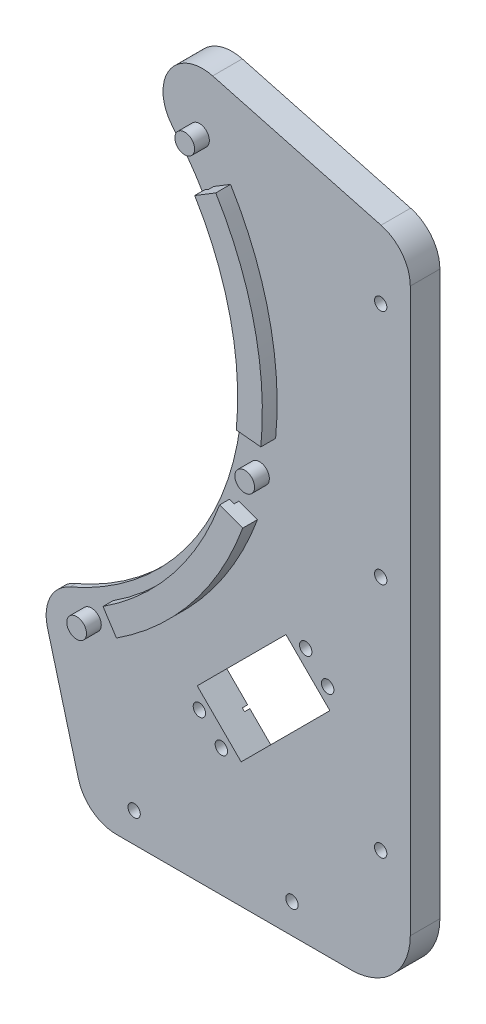
SolidWorks part; units mm, degrees
ref_plane "Front Plane" through (0, 0, 0) normal (0, 0, 1) x (1, 0, 0)
ref_plane "Top Plane" through (0, 0, 0) normal (0, 1, 0) x (1, 0, 0)
ref_plane "Right Plane" through (0, 0, 0) normal (1, 0, 0) x (0, 0, -1)
other "Configuration Table"
sketch "Sketch1" plane through (0, 0, 0) normal (0, 0, 1) x (1, 0, 0)
  line L3 (0, 0) -> (0, 95.25) construction
  line L4 (0, -106.7771) -> (0, 106.7771) construction
  line L5 (0, 0) -> (74.4694, 59.3874) construction
  line L6 (0, 0) -> (92.8619, -21.1951) construction
  line L7 (0, 0) -> (41.3274, -85.8173) construction
  line L8 (0, 0) -> (-41.3274, -85.8173) construction
  line L9 (0, 0) -> (-92.8619, -21.1951) construction
  line L10 (0, 0) -> (-74.4694, 59.3874) construction
  line L11 (-88.1918, 53.5711) -> (-82.7647, 50.2744)
  line L13 (-96.3816, -9.3854) -> (-102.7017, -10.0009)
  line L14 (-90.909, -33.3624) -> (-96.8703, -35.5502)
  line L15 (-56.2145, -86.5309) -> (-52.7551, -81.2059)
  circle A0 centre (0, 0) radius 95.25 construction
  circle A1 centre (-78.1929, 62.3568) radius 3.175
  circle A2 centre (-78.1929, 62.3568) radius 4.7625 construction
  circle A3 centre (-97.505, -22.2549) radius 3.175
  circle A4 centre (-97.505, -22.2549) radius 4.7625 construction
  circle A5 centre (-43.3938, -90.1081) radius 3.175
  circle A6 centre (-43.3938, -90.1081) radius 4.7625 construction
  circle A7 centre (0, 0) radius 96.8375 construction
  arc A8 (-82.7647, 50.2744) -> (-96.3816, -9.3854) centre (0, 0) ccw
  arc A9 (-88.1918, 53.5711) -> (-102.7017, -10.0009) centre (0, 0) ccw
  arc A10 (-56.2145, -86.5309) -> (-96.8703, -35.5502) centre (0, 0) cw
  arc A11 (-52.7551, -81.2059) -> (-90.909, -33.3624) centre (0, 0) cw
  point P23 (0, 0)
  dimension "D1" = 190.5
  dimension "D2" = 9.525
  dimension "D3" = 6.35
  dimension "D4" = 7
  dimension "D5" = 6.35
  dimension "D6" = 12.7
  dimension "D7" = 12.7
extrude "Boss-Extrude1" add sketch "Sketch1" along normal blind 4.7625
sketch "Sketch2" plane through (0, 0, 0) normal (0, 0, 1) x (1, 0, 0)
  line L0 (0, 0) -> (-41.3274, -85.8173) construction
  line L1 (0, 0) -> (-92.8619, -21.1951) construction
  line L2 (0, 0) -> (-74.4694, 59.3874) construction
  line L3 (0, 0) -> (-41.3274, -85.8173) construction
  line L4 (0, 0) -> (-92.8619, -21.1951) construction
  line L5 (0, 0) -> (-74.4694, 59.3874) construction
  line L6 (-82.4301, 80.9271) -> (-136.637, 66.4024)
  line L7 (127, 127) -> (-127, 127) construction
  line L8 (127, 127) -> (127, -127) construction
  line L9 (127, -127) -> (-127, -127) construction
  line L10 (-127, 127) -> (-127, -127) construction
  line L11 (127, 127) -> (-127, -127) construction
  line L12 (127, -127) -> (-127, 127) construction
  line L13 (-146.05, 54.1351) -> (-146.05, -127)
  line L14 (-127, -146.05) -> (-51.4696, -146.05)
  line L15 (-39.2023, -136.637) -> (-29.2478, -99.4863)
  line L16 (-127, 44.45) -> (-146.05, 44.45) construction
  line L17 (-107.95, -127) -> (-107.95, -146.05) construction
  line L18 (-136.525, 44.45) -> (-136.525, -107.95) construction
  circle A0 centre (0, 0) radius 95.25 construction
  circle A1 centre (0, 0) radius 95.25 construction
  arc A2 (-69.55, 60.3374) -> (-36.4829, -84.5388) centre (0, 0) ccw
  arc A3 (-36.4829, -84.5388) -> (-29.2478, -99.4863) centre (-41.5151, -96.1993) cw
  arc A4 (-69.55, 60.3374) -> (-82.4301, 80.9271) centre (-79.1431, 68.6598) ccw
  arc A5 (-136.637, 66.4024) -> (-146.05, 54.1351) centre (-133.35, 54.1351) ccw
  arc A6 (-146.05, -127) -> (-127, -146.05) centre (-127, -127) ccw
  arc A7 (-51.4696, -146.05) -> (-39.2023, -136.637) centre (-51.4696, -133.35) ccw
  circle A8 centre (-136.525, 44.45) radius 1.9844
  circle A9 centre (-136.525, -31.75) radius 1.9844
  circle A10 centre (-136.525, -107.95) radius 1.9844
  circle A11 centre (-57.15, -136.525) radius 1.9844
  circle A12 centre (-107.95, -136.525) radius 1.9844
  point P38 (-136.525, 44.45)
  point P39 (-107.95, -136.525)
  point P42 (-136.525, -31.75)
  dimension "D1" = 92.075
  dimension "D9" = 12.7
  dimension "D10" = 3.9688
  dimension "D2" = 127
  dimension "D3" = 254
  dimension "D4" = 19.05
  dimension "D5" = 75
  dimension "D6" = 75
  dimension "D7" = 3.81
  dimension "D8" = 3.81
  dimension "D11" = 19.05
  dimension "D12" = 50.8
  dimension "D13" = 19.05
  dimension "D14" = 152.4
extrude "Boss-Extrude2" add sketch "Sketch2" against normal blind 9.525
sketch "Sketch3" plane through (0, 0, 4.7625) normal (0, 0, 1) x (1, 0, 0)
  line L2 (-82.7647, 50.2744) -> (-88.1918, 53.5711) construction
  line L3 (-102.7017, -10.0009) -> (-96.3816, -9.3854) construction
  line L6 (-81.4079, 49.4502) -> (-88.1918, 53.5711)
  line L7 (-102.7017, -10.0009) -> (-94.8016, -9.2316)
  line L8 (0, 0) -> (-92.8619, -21.1951) construction
  line L9 (0, 0) -> (-92.8619, -21.1951) construction
  line L10 (-96.8703, -35.5502) -> (-89.4187, -32.8155)
  line L11 (-51.8903, -79.8746) -> (-56.2145, -86.5309)
  arc A2 (-82.7647, 50.2744) -> (-96.3816, -9.3854) centre (0, 0) ccw construction
  arc A3 (-88.1918, 53.5711) -> (-102.7017, -10.0009) centre (0, 0) ccw construction
  arc A6 (-82.7647, 50.2744) -> (-96.3816, -9.3854) centre (0, 0) ccw construction
  arc A7 (-88.1918, 53.5711) -> (-102.7017, -10.0009) centre (0, 0) ccw
  arc A8 (-81.4079, 49.4502) -> (-94.8016, -9.2316) centre (0, 0) ccw
  arc A9 (-52.7551, -81.2059) -> (-90.909, -33.3624) centre (0, 0) cw construction
  arc A10 (-51.8903, -79.8746) -> (-89.4187, -32.8155) centre (0, 0) cw
  arc A11 (-56.2145, -86.5309) -> (-96.8703, -35.5502) centre (0, 0) cw
  dimension "D1" = 1.5875
extrude "Boss-Extrude3" add sketch "Sketch3" against normal blind 3.175
mirror "Mirror2" about plane through (0, 0, 0) normal (1, 0, 0) of bodies 108
delete or keep bodies "Body-Delete/Keep 1" type delete bodies bodies 108
sketch "Sketch5" plane through (0, 0, 0) normal (0, 0, 1) x (1, 0, 0)
  line L0 (98.8111, -84.3861) -> (91.5986, -91.5986) construction
  line L1 (106.0236, -63.0315) -> (77.4565, -91.5986)
  line L2 (106.0236, -63.0315) -> (120.1657, -77.1736)
  line L3 (120.1657, -77.1736) -> (91.5986, -105.7407)
  line L4 (77.4565, -91.5986) -> (91.5986, -105.7407)
  line L5 (106.0236, -63.0315) -> (91.5986, -105.7407) construction
  line L6 (120.1657, -77.1736) -> (77.4565, -91.5986) construction
  line L7 (71.842, -71.842) -> (45.5747, -98.1094) construction
  line L8 (78.1636, -97.9626) -> (85.2347, -105.0336) construction
  line L9 (112.3876, -63.7386) -> (119.4586, -70.8097) construction
  line L10 (115.9231, -67.2741) -> (81.6991, -101.4981) construction
  line L11 (127, -146.05) -> (51.4696, -146.05) construction
  circle A0 centre (0, 0) radius 116.84 construction
  circle A1 centre (0, 0) radius 101.6 construction
  circle A2 centre (91.5986, -91.5986) radius 27.94 construction
  circle A3 centre (119.4586, -70.8097) radius 2
  circle A4 centre (112.3876, -63.7386) radius 2
  circle A5 centre (78.1636, -97.9626) radius 2
  circle A6 centre (85.2347, -105.0336) radius 2
  point P3 (98.8111, -84.3861)
  dimension "D1" = 10
  dimension "D3" = 203.2
  dimension "D4" = 55.88
  dimension "D5" = 233.68
  dimension "D7" = 4
  dimension "D2" = 40.4
  dimension "D6" = 20
  dimension "D8" = 5
  dimension "D9" = 4
  dimension "D10" = 45
extrude "Cut-Extrude1" cut sketch "Sketch5" against normal through all
ref_plane "Plane1" through (91.5986, -91.5986, 0) normal (0.7071, -0.7071, 0) x (0, 0, -1)
sketch "Sketch6" plane through (91.5986, -91.5986, 0) normal (0.7071, -0.7071, 0) x (0, 0, -1)
  line L0 (9.525, 30.4) -> (9.525, 36.9)
  line L1 (9.525, 36.9) -> (7.825, 30.4)
  line L2 (7.825, 30.4) -> (9.525, 30.4)
  line L3 (0, 10.2) -> (9.525, 10.2) construction
  line L4 (0, 30.4) -> (0, -10)
  line L5 (0, -10) -> (9.525, -10)
  line L6 (9.525, -10) -> (9.525, 30.4)
  line L7 (9.525, 30.4) -> (0, 30.4)
  line L8 (0, 30.4) -> (0, -10) construction
  line L9 (0, -10) -> (9.525, -10) construction
  line L10 (9.525, -10) -> (9.525, 30.4) construction
  line L11 (9.525, 30.4) -> (0, 30.4) construction
  line L12 (7.825, -10) -> (9.525, -10)
  line L13 (9.525, -10) -> (9.525, -16.5)
  line L14 (9.525, -16.5) -> (7.825, -10)
  dimension "D2" = 6.5
  dimension "D3" = 1.7
  dimension "D1" = 0
extrude "Cut-Extrude2" cut sketch "Sketch6" against normal mid plane 1
chamfer "Chamfer1" distance 7.62 angle 50 1 edges at (89.7665, -20.4886, -9.525) tangent propagation no first distance on face at (71.3915, -16.2946, -4.7625)
